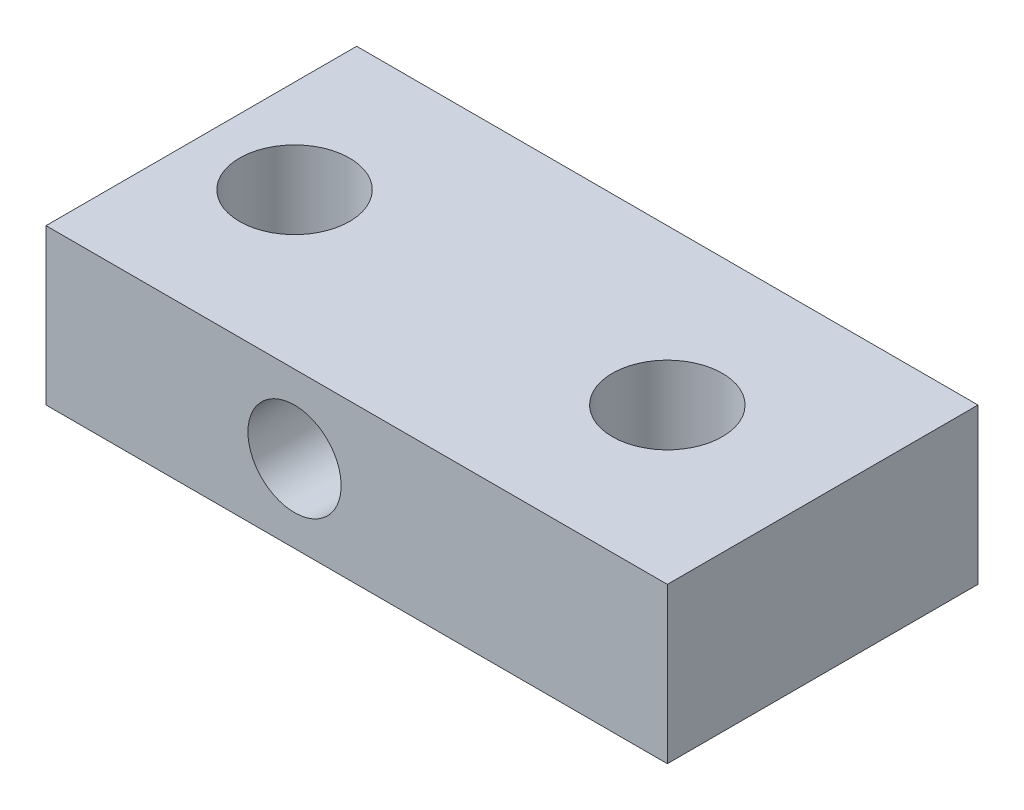
SolidWorks part; units mm, degrees
ref_plane "Front Plane" through (0, 0, 0) normal (0, 0, 1) x (1, 0, 0)
ref_plane "Top Plane" through (0, 0, 0) normal (0, 1, 0) x (1, 0, 0)
ref_plane "Right Plane" through (0, 0, 0) normal (1, 0, 0) x (0, 0, -1)
sketch "Sketch1" plane through (0, 0, 0) normal (0, 1, 0) x (1, 0, 0)
  line L1 (-12.7, -6.35) -> (12.7, -6.35)
  line L2 (-12.7, -6.35) -> (-12.7, 6.35)
  line L3 (-12.7, 6.35) -> (12.7, 6.35)
  line L4 (12.7, -6.35) -> (12.7, 6.35)
  line L5 (-12.7, -6.35) -> (12.7, 6.35) construction
  line L6 (-12.7, 6.35) -> (12.7, -6.35) construction
  point P0 (0, 0)
  dimension "D1" = 25.4
  dimension "D2" = 12.7
extrude "Boss-Extrude1" add sketch "Sketch1" along normal blind 6.35
sketch "Sketch2" plane through (0, 0, -6.35) normal (0, 0, -1) x (-1, 0, 0)
  line L0 (-12.7, 6.35) -> (-12.7, 0) construction
  line L1 (12.7, 6.35) -> (12.7, 0) construction
  circle A0 centre (2.54, 3.175) radius 1.905
  point P2 (5.6394, 3.175)
  point P3 (-12.7, 3.175)
  dimension "D1" = 3.81
  dimension "D2" = 10.16
extrude "Cut-Extrude1" cut sketch "Sketch2" against normal through all contours A0
hole_wizard "#8 Clearance Hole1" positions "Sketch3" profile "Sketch4" hole size "#8" standard "ANSI Inch" end condition through all
sketch "Sketch3" plane through (0, 6.35, 0) normal (0, 1, 0) x (1, 0, 0)
  line L0 (-8.89, 0) -> (6.35, 0) construction
  line L1 (-12.7, 6.35) -> (-12.7, -6.35) construction
  point P1 (-8.89, 0)
  point P2 (6.35, 0)
  point P8 (-8.89, 0)
  point P12 (6.35, 0)
  point P13 (-14.2805, 0)
  point P16 (-12.7, 0)
  dimension "D1" = 15.24
  dimension "D2" = 3.81
sketch "Sketch4" plane through (6.35, 6.35, 0) normal (1, 0, 0) x (0, 0, 1)
  line L0 (0, 0) -> (0, 6.35)
  line L1 (0, 6.35) -> (2.2479, 6.35)
  line L2 (2.2479, 6.35) -> (2.2479, 0)
  line L5 (2.2479, 0) -> (0, 0)
  line L11 (0, -6.35) -> (0, 107.95) construction
  dimension "Thru Hole Dia." = 4.4958
  dimension "Thru Hole Depth" = 6.35
